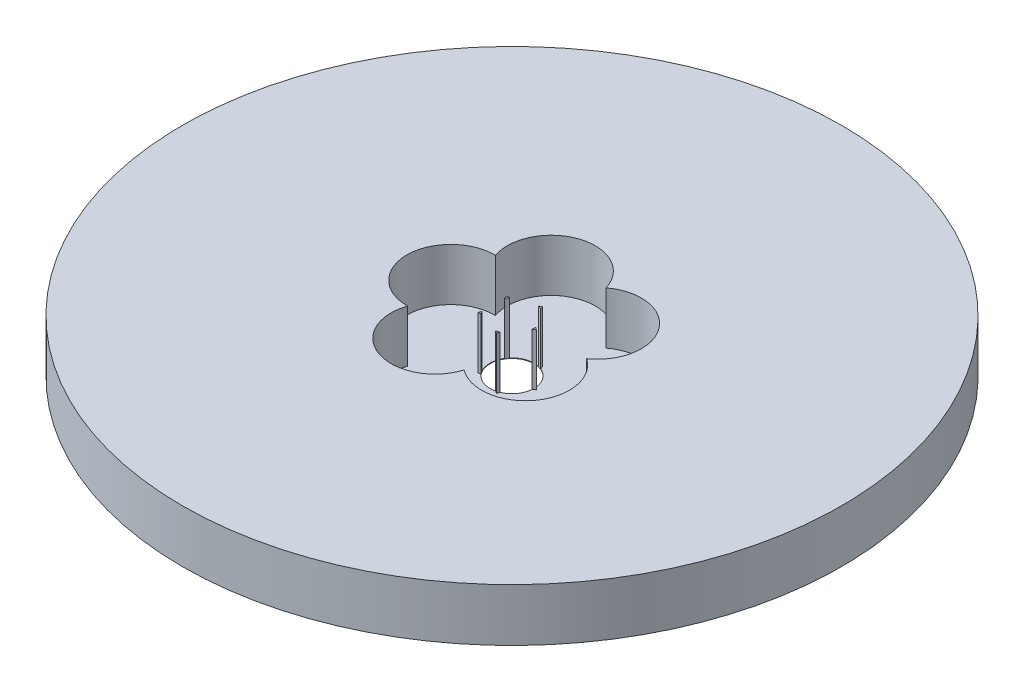
SolidWorks part; units mm, degrees
ref_plane "Front Plane" through (0, 0, 0) normal (0, 0, 1) x (1, 0, 0)
ref_plane "Top Plane" through (0, 0, 0) normal (0, 1, 0) x (1, 0, 0)
ref_plane "Right Plane" through (0, 0, 0) normal (1, 0, 0) x (0, 0, -1)
sketch "Sketch1" plane through (0, 0, 0) normal (0, 1, 0) x (1, 0, 0)
  circle A0 centre (0, 0) radius 75
  dimension "FLANGE_OD" = 150
extrude "Boss-Extrude1" add sketch "Sketch1" along normal blind 12
sketch "Sketch2" plane through (0, 0, 0) normal (0, 1, 0) x (1, 0, 0)
  circle A0 centre (0, 0) radius 5
  dimension "BORE_D" = 10
extrude "Cut-Extrude1" cut sketch "Sketch2" along normal through all
sketch "Sketch3" plane through (0, 12, 0) normal (0, 1, 0) x (1, 0, 0)
  circle A0 centre (0, 0) radius 13.9247 construction
  circle A1 centre (-13.9247, 0) radius 10
  dimension "BOLT_D" = 20
  dimension "BOLT_PCD" = 27.8494
extrude "Cut-Extrude2" cut sketch "Sketch3" against normal blind 11.8731
pattern_circular "CirPattern1" count 5 over 360 about axis through (0, 0, 0) along (0, 1, 0) of "Cut-Extrude2"
